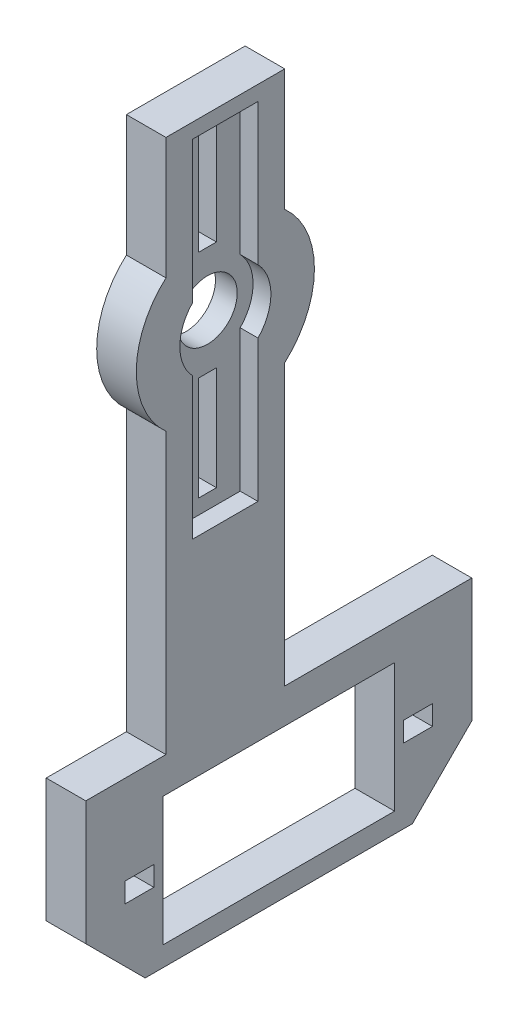
SolidWorks part; units mm, degrees
ref_plane "Front Plane" through (0, 0, 0) normal (0, 0, 1) x (1, 0, 0)
ref_plane "Top Plane" through (0, 0, 0) normal (0, 1, 0) x (1, 0, 0)
ref_plane "Right Plane" through (0, 0, 0) normal (1, 0, 0) x (0, 0, -1)
sketch "Sketch1" plane through (0, 0, 0) normal (1, 0, 0) x (0, 0, -1)
  circle A0 centre (52, -20) radius 9
extrude "Boss-Extrude1" add sketch "Sketch1" along normal blind 4 from offset 70.4 offset against normal yes
sketch "Sketch2" plane through (0, 0, 0) normal (0, 0, 1) x (1, 0, 0)
  line L1 (-70.4, -56) -> (-66.4, -56)
  line L2 (-70.4, -56) -> (-70.4, -1)
  line L3 (-70.4, -1) -> (-66.4, -1)
  line L4 (-66.4, -56) -> (-66.4, -1)
extrude "Boss-Extrude2" add sketch "Sketch2" along normal blind 12 from offset 58 offset against normal yes
sketch "Sketch3" plane through (0, 0, 0) normal (0, 0, 1) x (1, 0, 0)
  line L1 (-70.4, -73.5) -> (-66.4, -73.5)
  line L2 (-70.4, -73.5) -> (-70.4, -55)
  line L3 (-70.4, -55) -> (-66.4, -55)
  line L4 (-66.4, -73.5) -> (-66.4, -55)
extrude "Boss-Extrude3" add sketch "Sketch3" along normal blind 39 from offset 76.9 offset against normal yes
sketch "Sketch4" plane through (0, 0, 0) normal (1, 0, 0) x (0, 0, -1)
  line L0 (36.9, -74.5) -> (44.9, -74.5)
  line L1 (44.9, -74.5) -> (36.9, -66.5)
  line L2 (36.9, -66.5) -> (36.9, -74.5)
extrude "Boss-Extrude4" add sketch "Sketch4" along normal blind 6 from offset 71.4 separate body offset against normal yes
combine bodies "Combine1" operation type subtract main body 103 bodies to subtract 104
sketch "Sketch5" plane through (0, 0, 0) normal (1, 0, 0) x (0, 0, -1)
  line L0 (77.9, -74.5) -> (69.9, -74.5)
  line L1 (69.9, -74.5) -> (77.9, -66.5)
  line L2 (77.9, -66.5) -> (77.9, -74.5)
extrude "Boss-Extrude5" add sketch "Sketch5" along normal blind 6 from offset 71.4 separate body offset against normal yes
combine bodies "Combine2" operation type subtract main body 105 bodies to subtract 106
sketch "Sketch6" plane through (0, 0, 0) normal (1, 0, 0) x (0, 0, -1)
  circle A0 centre (52, -20) radius 4.6
extrude "Boss-Extrude6" add sketch "Sketch6" along normal blind 2.3 from offset 68.2 separate body offset against normal yes
combine bodies "Combine3" operation type subtract main body 107 bodies to subtract 108
sketch "Sketch7" plane through (0, 0, 0) normal (0, 0, 1) x (1, 0, 0)
  line L1 (-68.2, -20) -> (-65.9, -20)
  line L2 (-68.2, -20) -> (-68.2, -2.5)
  line L3 (-68.2, -2.5) -> (-65.9, -2.5)
  line L4 (-65.9, -20) -> (-65.9, -2.5)
extrude "Boss-Extrude7" add sketch "Sketch7" along normal blind 6.6 from offset 55.3 separate body offset against normal yes
combine bodies "Combine4" operation type subtract main body 109 bodies to subtract 110
sketch "Sketch8" plane through (0, 0, 0) normal (0, 0, 1) x (1, 0, 0)
  line L1 (-71.4, -14.5) -> (-65.4, -14.5)
  line L2 (-71.4, -14.5) -> (-71.4, -4)
  line L3 (-71.4, -4) -> (-65.4, -4)
  line L4 (-65.4, -14.5) -> (-65.4, -4)
extrude "Boss-Extrude8" add sketch "Sketch8" along normal blind 1.8 from offset 52.9 separate body offset against normal yes
combine bodies "Combine5" operation type subtract main body 111 bodies to subtract 112
sketch "Sketch9" plane through (0, 0, 0) normal (0, 0, 1) x (1, 0, 0)
  line L1 (-68.2, -37.5) -> (-65.9, -37.5)
  line L2 (-68.2, -37.5) -> (-68.2, -20)
  line L3 (-68.2, -20) -> (-65.9, -20)
  line L4 (-65.9, -37.5) -> (-65.9, -20)
extrude "Boss-Extrude9" add sketch "Sketch9" along normal blind 6.6 from offset 55.3 separate body offset against normal yes
combine bodies "Combine6" operation type subtract main body 113 bodies to subtract 114
sketch "Sketch10" plane through (0, 0, 0) normal (0, 0, 1) x (1, 0, 0)
  line L1 (-71.4, -36) -> (-65.4, -36)
  line L2 (-71.4, -36) -> (-71.4, -25.5)
  line L3 (-71.4, -25.5) -> (-65.4, -25.5)
  line L4 (-65.4, -36) -> (-65.4, -25.5)
extrude "Boss-Extrude10" add sketch "Sketch10" along normal blind 1.8 from offset 52.9 separate body offset against normal yes
combine bodies "Combine7" operation type subtract main body 115 bodies to subtract 116
sketch "Sketch11" plane through (0, 0, 0) normal (1, 0, 0) x (0, 0, -1)
  circle A0 centre (52, -20) radius 3
extrude "Boss-Extrude11" add sketch "Sketch11" along normal blind 6 from offset 71.4 separate body offset against normal yes
combine bodies "Combine8" operation type subtract main body 117 bodies to subtract 118
sketch "Sketch12" plane through (0, 0, 0) normal (0, 0, 1) x (1, 0, 0)
  line L1 (-71.4, -71.5) -> (-65.4, -71.5)
  line L2 (-71.4, -71.5) -> (-71.4, -58.5)
  line L3 (-71.4, -58.5) -> (-65.4, -58.5)
  line L4 (-65.4, -71.5) -> (-65.4, -58.5)
extrude "Boss-Extrude12" add sketch "Sketch12" along normal blind 23.4 from offset 69.1 separate body offset against normal yes
combine bodies "Combine9" operation type subtract main body 119 bodies to subtract 120
sketch "Sketch13" plane through (0, 0, 0) normal (0, 0, 1) x (1, 0, 0)
  line L1 (-71.4, -66) -> (-65.4, -66)
  line L2 (-71.4, -66) -> (-71.4, -64)
  line L3 (-71.4, -64) -> (-65.4, -64)
  line L4 (-65.4, -66) -> (-65.4, -64)
extrude "Boss-Extrude13" add sketch "Sketch13" along normal blind 2.9 from offset 72.925 separate body offset against normal yes
combine bodies "Combine10" operation type subtract main body 121 bodies to subtract 122
sketch "Sketch14" plane through (0, 0, 0) normal (0, 0, 1) x (1, 0, 0)
  line L1 (-71.4, -66) -> (-65.4, -66)
  line L2 (-71.4, -66) -> (-71.4, -64)
  line L3 (-71.4, -64) -> (-65.4, -64)
  line L4 (-65.4, -66) -> (-65.4, -64)
extrude "Boss-Extrude14" add sketch "Sketch14" along normal blind 2.9 from offset 44.775 separate body offset against normal yes
combine bodies "Combine11" operation type subtract main body 123 bodies to subtract 124
